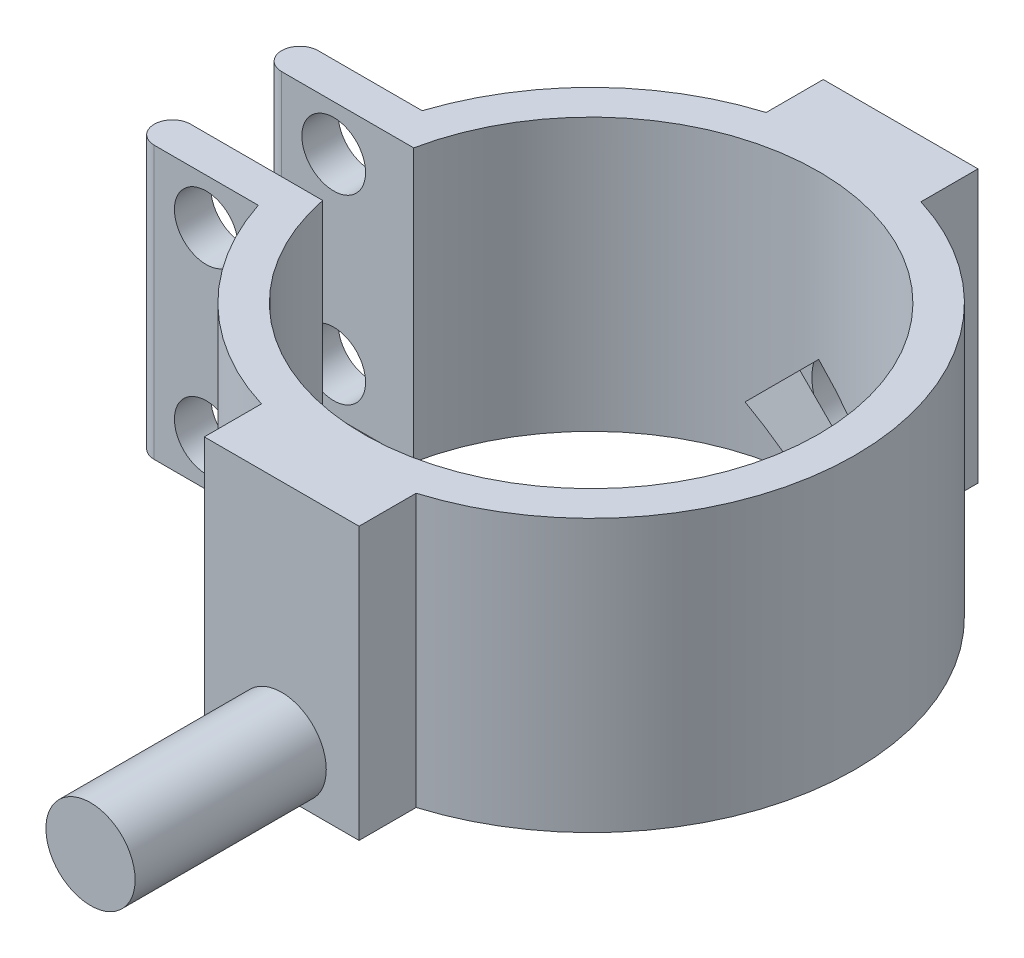
SolidWorks part; units mm, degrees
ref_plane "Front Plane" through (0, 0, 0) normal (0, 0, 1) x (1, 0, 0)
ref_plane "Top Plane" through (0, 0, 0) normal (0, 1, 0) x (1, 0, 0)
ref_plane "Right Plane" through (0, 0, 0) normal (1, 0, 0) x (0, 0, -1)
sketch "Sketch1" plane through (0, 0, 0) normal (0, 1, 0) x (1, 0, 0)
  line L0 (-12.5, -17.5) -> (-12.5, 17.5) construction
  line L1 (-30, -17.5) -> (30, -17.5)
  line L2 (-30, -17.5) -> (-30, 17.5)
  line L3 (-30, 17.5) -> (30, 17.5)
  line L4 (30, -17.5) -> (30, 17.5)
  line L5 (-30, -17.5) -> (30, 17.5) construction
  line L6 (-30, 17.5) -> (30, -17.5) construction
  line L7 (-12.2474, -2.5) -> (-12.5, -2.5)
  line L8 (-12.2474, 2.5) -> (-12.5, 2.5)
  line L9 (-12.5, -2.5) -> (-19.5, -2.5)
  line L10 (-12.5, 2.5) -> (-19.5, 2.5)
  line L11 (-13.784, 4.5) -> (-19.5, 4.5)
  line L12 (-13.784, 4.5) -> (-13.784, 4.5)
  line L13 (-13.784, -4.5) -> (-13.784, -4.5)
  line L14 (-13.784, -4.5) -> (-19.5, -4.5)
  line L15 (-30, -14.5) -> (30, -14.5) construction
  line L16 (-4.25, -13.8632) -> (-4.25, -14.5)
  line L17 (4.25, -14.5) -> (4.25, -13.8632)
  line L18 (0, 0) -> (10.0696, 0) construction
  line L19 (-4.25, -14.5) -> (4.25, -14.5) construction
  line L20 (-4.25, -14.5) -> (-4.25, -17)
  line L21 (-4.25, -17) -> (4.25, -17)
  line L22 (4.25, -14.5) -> (4.25, -17)
  line L23 (4.25, 14.5) -> (4.25, 17)
  line L24 (-4.25, 17) -> (4.25, 17)
  line L25 (-4.25, 14.5) -> (-4.25, 17)
  line L26 (-4.25, 14.5) -> (4.25, 14.5) construction
  line L27 (4.25, 14.5) -> (4.25, 13.8632)
  line L28 (-4.25, 13.8632) -> (-4.25, 14.5)
  circle A0 centre (0, 0) radius 12.5 construction
  arc A1 (-12.2474, 2.5) -> (-12.2474, -2.5) centre (0, 0) cw
  arc A2 (-13.784, 4.5) -> (-13.784, -4.5) centre (0, 0) cw
  arc A3 (-19.5, 2.5) -> (-19.5, 4.5) centre (-19.5, 3.5) cw
  arc A4 (-19.5, -2.5) -> (-19.5, -4.5) centre (-19.5, -3.5) ccw
  point P0 (0, 0)
  point P15 (-12.5, 0)
  point P32 (0, 14.5)
  point P40 (0, -14.5)
  dimension "D3" = 25
  dimension "D1" = 60
  dimension "D2" = 35
  dimension "D4" = 7
  dimension "D6" = 5
  dimension "D7" = 8.5
  dimension "D8" = 0.5
  dimension "D5" = 2
extrude "Boss-Extrude1" add sketch "Sketch1" along normal mid plane 4.951 contours L9 A4 L14 A2 L11 A3 L10 L8 A1 L7 | L17 A2 L16 L20 L21 L22 | L28 A2 L27 L23 L24 L25 region at (12.9545, 0, 0) region at (0, 0, 15.6382) region at (0, 0, -15.6382)
sketch "Sketch6" plane through (0, 2.4755, 0) normal (0, 1, 0) x (1, 0, 0)
  line L12 (-12.2474, -2.5) -> (-19.5, -2.5)
  line L13 (-19.5, -4.5) -> (-13.784, -4.5)
  line L14 (-4.25, -13.8632) -> (-4.25, -17)
  line L15 (-4.25, -17) -> (4.25, -17)
  line L17 (4.25, -17) -> (4.25, -13.8632)
  line L18 (4.25, 13.8632) -> (4.25, 17)
  line L19 (4.25, 17) -> (-4.25, 17)
  line L21 (-4.25, 17) -> (-4.25, 13.8632)
  line L22 (-13.784, 4.5) -> (-19.5, 4.5)
  line L23 (-19.5, 2.5) -> (-12.2474, 2.5)
  line L24 (-12.2474, -2.5) -> (-19.5, -2.5)
  line L25 (-19.5, -4.5) -> (-13.784, -4.5)
  line L26 (-4.25, -13.8632) -> (-4.25, -17)
  line L27 (-4.25, -17) -> (4.25, -17)
  line L29 (4.25, -17) -> (4.25, -13.8632)
  line L30 (4.25, 13.8632) -> (4.25, 17)
  line L31 (4.25, 17) -> (-4.25, 17)
  line L33 (-4.25, 17) -> (-4.25, 13.8632)
  line L34 (-13.784, 4.5) -> (-19.5, 4.5)
  line L35 (-19.5, 2.5) -> (-12.2474, 2.5)
  arc A6 (-19.5, -2.5) -> (-19.5, -4.5) centre (-19.5, -3.5) ccw
  arc A7 (-13.784, -4.5) -> (-4.25, -13.8632) centre (0, 0) ccw
  arc A8 (4.25, -13.8632) -> (4.25, 13.8632) centre (0, 0) ccw
  arc A9 (-4.25, 13.8632) -> (-13.784, 4.5) centre (0, 0) ccw
  arc A10 (-19.5, 4.5) -> (-19.5, 2.5) centre (-19.5, 3.5) ccw
  arc A11 (-12.2474, -2.5) -> (-12.2474, 2.5) centre (0, 0) ccw
  arc A12 (-19.5, -2.5) -> (-19.5, -4.5) centre (-19.5, -3.5) ccw
  arc A13 (-13.784, -4.5) -> (-4.25, -13.8632) centre (0, 0) ccw
  arc A14 (4.25, -13.8632) -> (4.25, 13.8632) centre (0, 0) ccw
  arc A15 (-4.25, 13.8632) -> (-13.784, 4.5) centre (0, 0) ccw
  arc A16 (-19.5, 4.5) -> (-19.5, 2.5) centre (-19.5, 3.5) ccw
  arc A17 (-12.2474, -2.5) -> (-12.2474, 2.5) centre (0, 0) ccw
  dimension "D1" = 0
extrude "Boss-Extrude3" add sketch "Sketch6" along normal blind 10
sketch "Sketch3" plane through (0, 0, 4.5) normal (0, 0, 1) x (1, 0, 0)
  line L2 (-13.784, -2.4755) -> (-19.5, -2.4755) construction
  line L3 (-16.642, 12.4755) -> (-16.642, 9.9755) construction
  line L4 (-19.5, 12.4755) -> (-13.784, 12.4755) construction
  circle A0 centre (-16.642, 0) radius 1.75
  circle A1 centre (-16.642, 9.9755) radius 1.75
  point P0 (-16.642, -2.4755)
  dimension "D1" = 3.5
  dimension "D2" = 2.5
extrude "Cut-Extrude1" cut sketch "Sketch3" against normal up to surface (9 mm away) up to face at (-16.642, 5, -4.5)
sketch "Sketch4" plane through (0, 0, -17) normal (0, 0, 1) x (1, 0, 0)
  circle A1 centre (0, 0) radius 2.45
  dimension "D1" = 4.9
extrude "Boss-Extrude2" add sketch "Sketch4" against normal blind 10.5
sketch "Sketch7" plane through (0, 0, 17) normal (0, 0, 1) x (1, 0, 0)
  line L1 (0, 3.5355) -> (-3.5355, 0)
  line L2 (-3.5355, 0) -> (0, -3.5355)
  line L3 (0, -3.5355) -> (3.5355, 0)
  line L4 (3.5355, 0) -> (0, 3.5355)
  circle A0 centre (0, 0) radius 2.5 construction
  circle A1 centre (0, 0) radius 2.5 construction
  line M1 (-4.25, -2.4755) -> (4.25, -2.4755)
  dimension "D1" = 5
extrude "Cut-Extrude10" cut sketch "Sketch7" against normal up to surface (2.545 mm away) from offset 2 contours L3 L4 L1 L2 M1 region at (0, 0.1331, 17) up to face at (0.1263, 5, 0) offset against normal yes
sketch "Sketch8" plane through (0, 0, 17) normal (0, 0, 1) x (1, 0, 0)
  line L4 (0, 3.5355) -> (-3.5355, 0)
  line L5 (-3.5355, 0) -> (0, -3.5355)
  line L6 (0, -3.5355) -> (3.5355, 0)
  line L7 (3.5355, 0) -> (0, 3.5355)
  line L8 (0, 3.5355) -> (-3.5355, 0) construction
  line L9 (-3.5355, 0) -> (0, -3.5355) construction
  line L10 (0, -3.5355) -> (3.5355, 0) construction
  line L11 (3.5355, 0) -> (0, 3.5355) construction
  circle A0 centre (0, 0) radius 2.875
  dimension "D2" = 5.75
  dimension "D1" = 0
extrude "Cut-Extrude11" cut sketch "Sketch8" against normal up to surface (2 mm away) up to face at (0, -0.2831, 15)
mirror "Mirror1" about plane through (0, 0, 0) normal (0, 0, 1) of bodies 108
delete or keep bodies "Body-Delete/Keep 1" type delete bodies bodies 108
equation "\"a\"= 1"
equation "\"b\"= 1"
equation "\"c\"= 1"
equation "\"d\"= 1"
equation "\"e\"= 1"
equation "\"x\"= 1"
equation "\"y\"= 1"
equation "\"z\"= 1"
